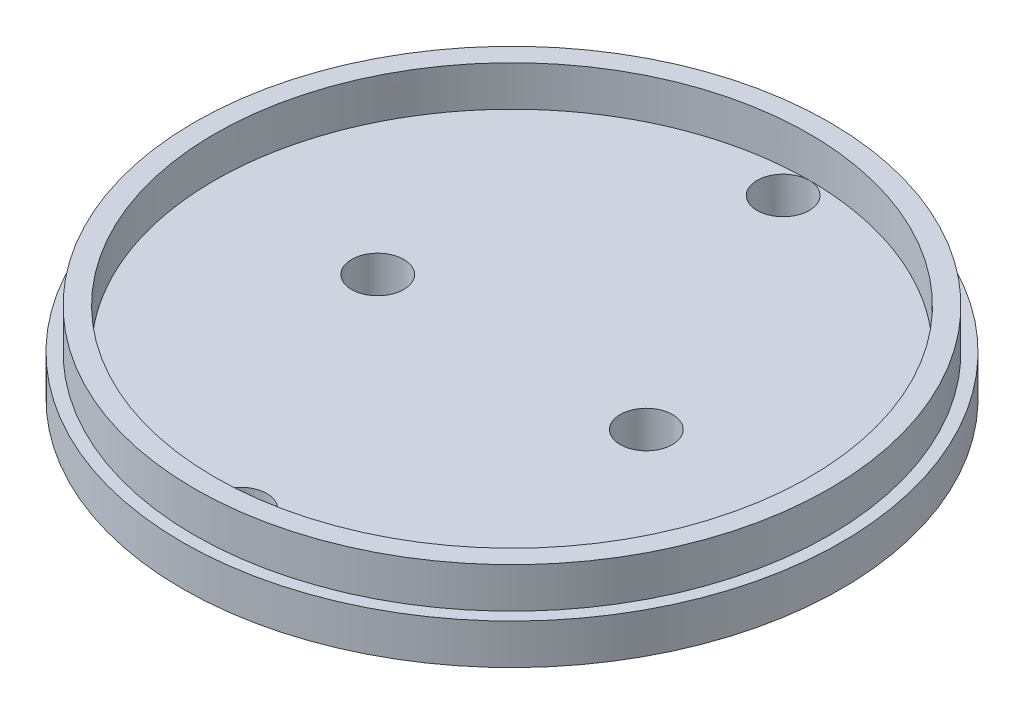
SolidWorks part; units mm, degrees
ref_plane "Front Plane" through (0, 0, 0) normal (0, 0, 1) x (1, 0, 0)
ref_plane "Top Plane" through (0, 0, 0) normal (0, 1, 0) x (1, 0, 0)
ref_plane "Right Plane" through (0, 0, 0) normal (1, 0, 0) x (0, 0, -1)
sketch "Sketch1" plane through (0, 0, 0) normal (0, 1, 0) x (1, 0, 0)
  circle A0 centre (0, 0) radius 40.9
  circle A1 centre (0, 0) radius 39.4
  circle A2 centre (0, 0) radius 36.9
  dimension "D1" = 81.8
  dimension "D2" = 78.8
  dimension "D3" = 2.5
extrude "Boss-Extrude1" add sketch "Sketch1" along normal blind 5 contours A1 A2 region at (-38.2856, 0, 0)
extrude "Boss-Extrude2" add sketch "Sketch1<4>" against normal blind 5 contours A1 A2 | A2 | A0 A1 region at (-39.7432, 0, 0) region at (-38.2856, 0, 0) region at (0, 0, 0)
sketch "Sketch1<4>" plane through (0, 0, 0) normal (0, 1, 0) x (1, 0, 0) same geometry as "Sketch1"
sketch "Sketch4" plane through (0, -5, 0) normal (0, -1, 0) x (1, 0, 0)
  line L0 (16.6687, 0) -> (-16.6688, 0) construction
  line L1 (0, 33.655) -> (0, -33.655) construction
  circle A0 centre (-16.6688, 0) radius 3.2385
  circle A1 centre (16.6687, 0) radius 3.2385
  circle A2 centre (0, 33.655) radius 3.2385
  circle A3 centre (0, -33.655) radius 3.2385
  point P5 (0, 0)
  point P11 (0, 0)
  dimension "D2" = 6.477
  dimension "D4" = 6.477
  dimension "D1" = 33.3375
  dimension "D3" = 67.31
extrude "Cut-Extrude1" cut sketch "Sketch4" against normal through all both and the other way through all
